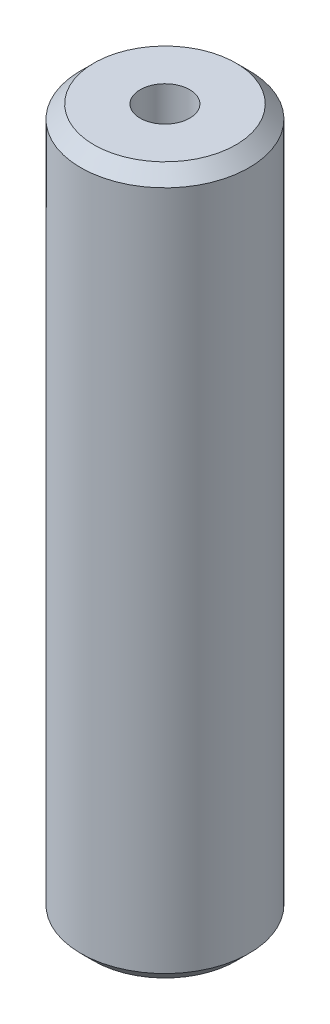
SolidWorks part; units mm, degrees
ref_plane "Front Plane" through (0, 0, 0) normal (0, 0, 1) x (1, 0, 0)
ref_plane "Top Plane" through (0, 0, 0) normal (0, 1, 0) x (1, 0, 0)
ref_plane "Right Plane" through (0, 0, 0) normal (1, 0, 0) x (0, 0, -1)
sketch "Sketch1" plane through (0, 0, 0) normal (0, 1, 0) x (1, 0, 0)
  circle A0 centre (0, 0) radius 15
  dimension "SHAFT_OD" = 30
extrude "Boss-Extrude1" add sketch "Sketch1" along normal blind 126.0038
sketch "Sketch2" plane through (0, 0, 0) normal (0, 1, 0) x (1, 0, 0)
  circle A0 centre (0, 0) radius 4.4123
  dimension "BORE_D" = 8.8246
extrude "Cut-Extrude1" cut sketch "Sketch2" along normal through all
chamfer "Chamfer1" distance 2.3525 angle 45 2 edges at (0, 126.0038, 15) (0, 0, 15)
